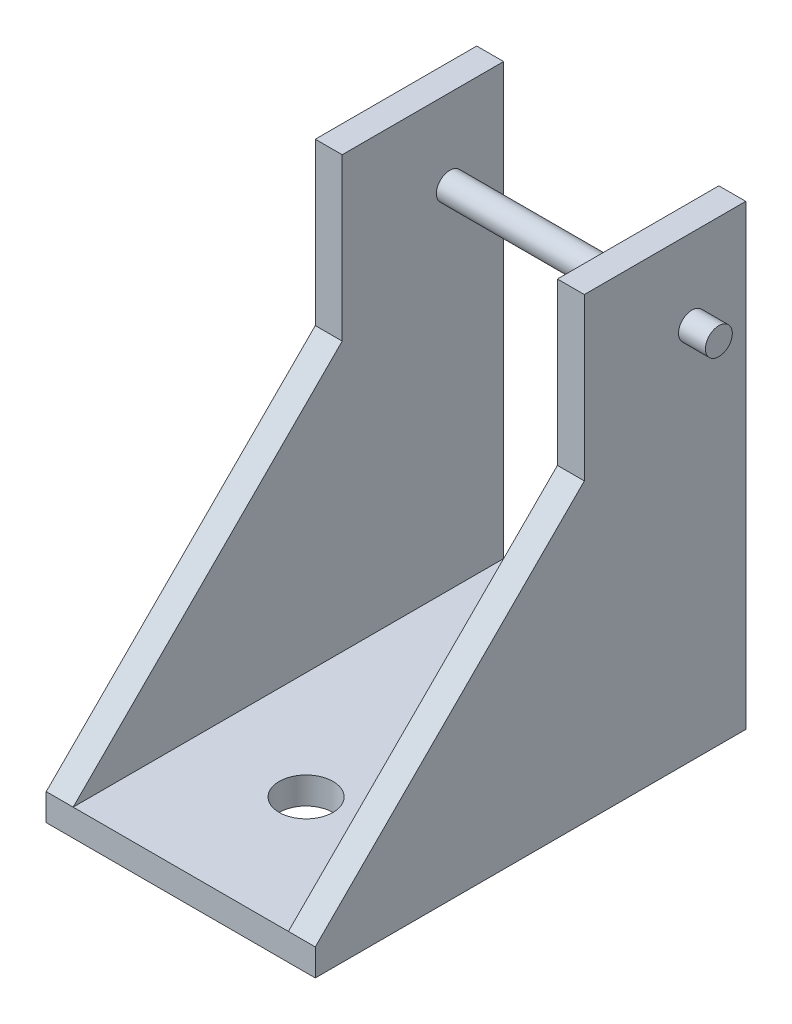
SolidWorks part; units mm, degrees
material "Plain Carbon Steel"
ref_plane "Front Plane" through (0, 0, 0) normal (0, 0, 1) x (1, 0, 0)
ref_plane "Top Plane" through (0, 0, 0) normal (0, 1, 0) x (1, 0, 0)
ref_plane "Right Plane" through (0, 0, 0) normal (1, 0, 0) x (0, 0, -1)
sketch "Sketch2" plane through (0, 0, 0) normal (0, 0, 1) x (1, 0, 0)
  line L1 (0, 0) -> (63.5, 0)
  line L2 (0, 0) -> (0, 6.35)
  line L3 (0, 6.35) -> (63.5, 6.35)
  line L4 (63.5, 0) -> (63.5, 6.35)
  dimension "D1" = 6.35
  dimension "D2" = 63.5
extrude "Base" add sketch "Sketch2" along normal blind 101.6
ref_plane "Plane1" through (31.75, 0, 0) normal (-1, 0, 0) x (0, 0, 1)
sketch "Sketch4" plane through (63.5, 0, 0) normal (1, 0, 0) x (0, 0, -1)
  line L0 (0, 107.95) -> (0, 6.35)
  line L1 (0, 107.95) -> (-38.1, 107.95)
  line L2 (0, 6.35) -> (-101.6, 6.35)
  line L3 (-101.6, 6.35) -> (0, 6.35) construction
  line L4 (-101.6, 6.35) -> (-38.1, 69.85)
  line L5 (-101.6, 0) -> (-101.6, 6.35) construction
  line L6 (-38.1, 107.95) -> (-38.1, 69.85)
  dimension "D1" = 38.1
  dimension "D2" = 45
extrude "Rib" add sketch "Sketch4" against normal blind 6.35
mirror "RibCopy" about plane through (31.75, 0, 0) normal (-1, 0, 0) of "Rib"
sketch "Sketch5" plane through (57.15, 0, 0) normal (-1, 0, 0) x (0, 0, 1)
  line L0 (101.6, 0) -> (0, 0) construction
  line L1 (0, 0) -> (0, 107.95) construction
  circle A0 centre (12.7, 88.9) radius 3.175
  dimension "D1" = 6.35
  dimension "D2" = 88.9
  dimension "D3" = 12.7
extrude "Cut-Extrude1" cut sketch "Sketch5" against normal through all and the other way through all
extrude "Boss-Extrude1" add sketch "Sketch5<2>" along normal blind 63.5 and the other way blind 12.7 separate body
sketch "Sketch5<2>" plane through (57.15, 0, 0) normal (-1, 0, 0) x (0, 0, 1) same geometry as "Sketch5"
sketch "Sketch6" plane through (0, 6.35, 0) normal (0, 1, 0) x (-1, 0, 0)
  line L0 (-57.15, 101.6) -> (-57.15, 0) construction
  line L1 (-31.75, 72.0236) -> (-31.75, 32.1145) construction
  circle A0 centre (-31.75, 72.0236) radius 6.35
  circle A1 centre (-31.75, 32.1145) radius 6.35
  dimension "D1" = 12.7
  dimension "D2" = 25.4
extrude "Cut-Extrude2" cut sketch "Sketch6" against normal up to next (6.35 mm away)
